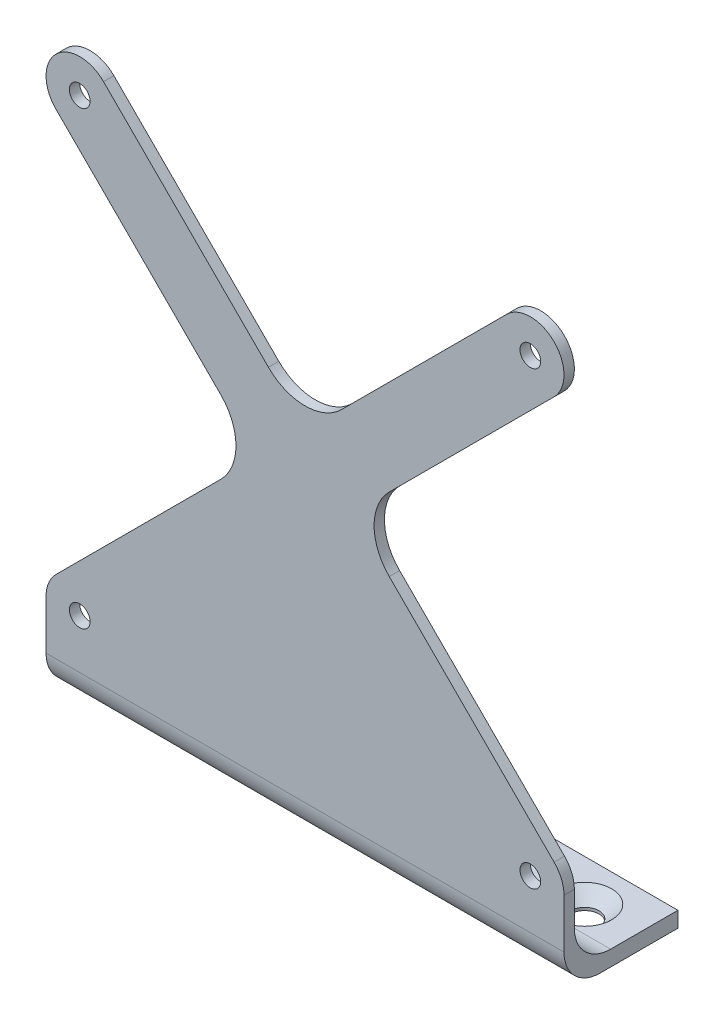
SolidWorks part; units mm, degrees
ref_plane "Plan de face" through (0, 0, 0) normal (0, 0, 1) x (1, 0, 0)
ref_plane "Plan de dessus" through (0, 0, 0) normal (0, 1, 0) x (1, 0, 0)
ref_plane "Plan de droite" through (0, 0, 0) normal (1, 0, 0) x (0, 0, -1)
sketch "Esquisse1" plane through (0, 0, 0) normal (0, 0, 1) x (1, 0, 0)
  line L1 (50, -55) -> (-50, -55)
  line L2 (50, -55) -> (50, 55)
  line L3 (50, 55) -> (-50, 55)
  line L4 (-50, -55) -> (-50, 55)
  line L5 (50, -55) -> (-50, 55) construction
  line L6 (50, 55) -> (-50, -55) construction
  point P0 (0, 0)
  dimension "D1" = 110
  dimension "D2" = 100
extrude "Boss.-Extru.1" add sketch "Esquisse1" along normal blind 2
sketch "Esquisse3" plane through (0, -55, 0) normal (0, -1, 0) x (1, 0, 0)
  line L0 (-50, 0) -> (50, 0)
  line L1 (-50, 0) -> (-50, -20)
  line L2 (50, 0) -> (50, -20)
  line L3 (-50, -20) -> (50, -20)
  dimension "D1" = 20
extrude "Boss.-Extru.2" add sketch "Esquisse3" against normal blind 3
hole_wizard "Fraisage pour vis à tête fraisée M51" positions "Esquisse4" profile "Esquisse5" countersink size "M5" standard "ISO" end condition through all
sketch "Esquisse4" plane through (0, -52, 0) normal (0, 1, 0) x (1, 0, 0)
  line L0 (-40, 12) -> (40, 12) construction
  line L2 (-50, 20) -> (50, 20) construction
  point P0 (-40, 12)
  point P2 (40, 12)
  point P10 (0, 12)
  dimension "D1" = 80
  dimension "D2" = 8
sketch "Esquisse5" plane through (-40, -52, -12) normal (1, 0, 0) x (0, 0, 1)
  line L0 (0, 0) -> (0, 3)
  line L1 (0, 3) -> (2.75, 3)
  line L2 (2.75, 3) -> (2.75, 2.45)
  line L3 (2.75, 2.45) -> (5.2, 0)
  line L5 (5.2, 0) -> (0, 0)
  line L6 (-2.75, 2.45) -> (-5.2, 0) construction
  line L11 (0, -6.35) -> (0, 107.95) construction
  dimension "Diamètre du perçage jusqu'au prochain" = 5.5
  dimension "Profondeur du perçage jusqu'au prochain" = 3
  dimension "Diamètre du fraisage entrant" = 10.4
  dimension "Angle du fraisage entrant" = 90
sketch "Esquisse6" plane through (0, 0, 2) normal (0, 0, 1) x (1, 0, 0)
  line L0 (-43.5, 48.5) -> (-43.5, 55) construction
  line L1 (43.5, -38.5) -> (-43.5, -38.5) construction
  line L2 (43.5, -38.5) -> (43.5, 48.5) construction
  line L3 (43.5, 48.5) -> (-43.5, 48.5) construction
  line L4 (-43.5, -38.5) -> (-43.5, 48.5) construction
  line L5 (43.5, -38.5) -> (-43.5, 48.5) construction
  line L6 (43.5, 48.5) -> (-43.5, -38.5) construction
  line L7 (-43.5, 48.5) -> (-50, 48.5) construction
  line L8 (-50, 55) -> (-50, -55) construction
  line L9 (50, 55) -> (-50, 55) construction
  circle A0 centre (-43.5, 48.5) radius 2
  circle A1 centre (43.5, 48.5) radius 2
  circle A2 centre (-43.5, -38.5) radius 2
  circle A3 centre (43.5, -38.5) radius 2
  point P0 (0, 5)
  point P9 (0, 0)
  dimension "D1" = 4
  dimension "D2" = 87
extrude "Enlèv. mat.-Extru.1" cut sketch "Esquisse6" against normal through all
fillet "Congé1" radius 7 2 edges at (0, -52, 0) (0, -55, 2)
sketch "Esquisse7" plane through (0, 0, 2) normal (0, 0, 1) x (1, 0, 0)
  line L0 (-48.0962, 43.9038) -> (-9.1924, 5)
  line L1 (50, 55) -> (-50, 55) construction
  line L2 (-48.0962, -33.9038) -> (-9.1924, 5)
  line L3 (-50, 55) -> (-50, -48) construction
  line L4 (-48.0962, 43.9038) -> (-38.9038, 53.0962) construction
  line L5 (-38.9038, 53.0962) -> (0, 14.1924)
  line L6 (0, 14.1924) -> (0, 55)
  line L7 (0, 55) -> (-50, 55)
  line L8 (-50, 55) -> (-50, -38.5)
  arc A0 (-38.9038, 53.0962) -> (-48.0962, 43.9038) centre (-43.5, 48.5) ccw
  arc A1 (-48.0962, -33.9038) -> (-50, -38.5) centre (-43.5, -38.5) ccw
  line M14 (-50, 55) -> (-50, -48)
  line M17 (50, 55) -> (-50, 55)
  dimension "D1" = 50
extrude "Enlèv. mat.-Extru.2" cut sketch "Esquisse7" against normal through all contours A0 L5 L6 M17 | A1 L2 L0 A0 L8 | A0 L7 M14 region at (-13.6324, 41.4119, 2) region at (-48.5481, 53.5481, 2) region at (-36.4119, 5, 2)
mirror "Symétrie1" about plane through (0, 0, 0) normal (1, 0, 0) of "Enlèv. mat.-Extru.2"
fillet "Congé2" radius 10 3 edges at (9.1924, 5, 1) (0, 14.1924, 1) (-9.1924, 5, 1)
